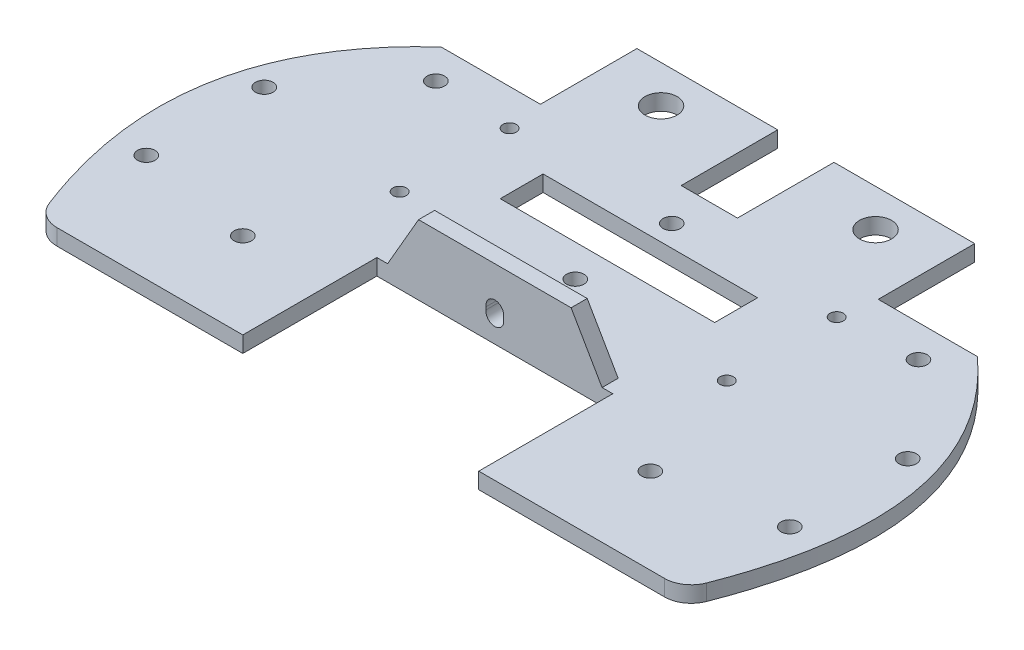
SolidWorks part; units mm, degrees
ref_plane "Front Plane" through (0, 0, 0) normal (0, 0, 1) x (1, 0, 0)
ref_plane "Top Plane" through (0, 0, 0) normal (0, 1, 0) x (1, 0, 0)
ref_plane "Right Plane" through (0, 0, 0) normal (1, 0, 0) x (0, 0, -1)
sketch "Sketch1" plane through (0, 0, 0) normal (0, 1, 0) x (1, 0, 0)
  line L0 (0, 0) -> (24.3409, 0) construction
  line L1 (-31.5, -11) -> (31.5, -11)
  line L2 (-31.5, -11) -> (-31.5, 11)
  line L3 (-31.5, 11) -> (31.5, 11)
  line L4 (31.5, -11) -> (31.5, 11)
  line L5 (-31.5, -11) -> (31.5, 11) construction
  line L6 (-31.5, 11) -> (31.5, -11) construction
  line L7 (0, 0) -> (0, 29.903) construction
  line L8 (-50, -11) -> (50, -11)
  line L9 (-5.25, 11) -> (5.25, 11)
  line L10 (-5.25, 11) -> (-5.25, -11)
  line L11 (-5.25, -11) -> (5.25, -11)
  line L12 (5.25, 11) -> (5.25, -11)
  line L13 (-5.25, 11) -> (5.25, -11) construction
  line L14 (-5.25, -11) -> (5.25, 11) construction
  line L15 (-60, -76) -> (60, -76)
  line L16 (-115.1518, -60) -> (108.3156, -60) construction
  line L28 (-22, -51) -> (22, -51)
  line L29 (-22, -51) -> (-22, -76)
  line L30 (-22, -76) -> (22, -76)
  line L31 (22, -51) -> (22, -76)
  line L32 (-22, -51) -> (22, -76) construction
  line L33 (-22, -76) -> (22, -51) construction
  circle A0 centre (-20, 0) radius 3
  circle A1 centre (20, 0) radius 3
  spline S0 degree 2 poles (-50, -11) (-77.2307, -35.6586) (-60, -76) knots 0 0 0 1 1 1
  spline S1 degree 2 poles (50, -11) (77.2307, -35.6586) (60, -76) knots 0 0 0 1 1 1
  point P0 (0, 0)
  point P13 (0, 0)
  point P20 (0, -11)
  point P23 (0, -76)
  point P40 (0, -63.5)
  dimension "D2" = 6
  dimension "D1" = 63
  dimension "D3" = 20
  dimension "D4" = 10.5
  dimension "D5" = 22
  dimension "D6" = 120
  dimension "D8" = 65
  dimension "D13" = 16
  dimension "D14" = 44
  dimension "D15" = 25
extrude "Boss-Extrude1" add sketch "Sketch1" along normal blind 3
fillet "Fillet1" radius 5 2 edges at (-60, 1.5, 76) (60, 1.5, 76)
sketch "Sketch2" plane through (0, 3, 0) normal (0, 1, 0) x (1, 0, 0)
  line L0 (0, 0) -> (0, -132.9136) construction
  line L1 (-56.6417, -76) -> (-22, -76) construction
  line L2 (0, -17) -> (-58.0491, -17) construction
  line L3 (-63.5757, -34) -> (6.6182, -34) construction
  line L5 (-5.25, -11) -> (5.25, -11) construction
  line L6 (-50, -11) -> (-31.5, -11) construction
  circle A0 centre (-60, -56) radius 1.625
  circle A1 centre (60, -56) radius 1.625
  circle A2 centre (-45, -17) radius 1.625
  circle A3 centre (-60, -34) radius 1.625
  circle A4 centre (60, -34) radius 1.625
  circle A5 centre (45, -17) radius 1.625
  circle A6 centre (0, -18) radius 1.625
  circle A7 centre (0, -36) radius 1.625
  dimension "D3" = 3.25
  dimension "D5" = 18
  dimension "D1" = 60
  dimension "D2" = 20
  dimension "D4" = 6
  dimension "D6" = 45
  dimension "D7" = 60
  dimension "D8" = 23
  dimension "D9" = 7
extrude "Cut-Extrude1" cut sketch "Sketch2" against normal up to surface (3 mm away) up to face at (0, 0, 28.5141)
sketch "Sketch3" plane through (0, 3, 0) normal (0, 1, 0) x (1, 0, 0)
  line L2 (0, 0) -> (0, -162.7456) construction
  line L3 (0, -76) -> (-36.7508, -76) construction
  line L4 (-5.25, -11) -> (5.25, -11) construction
  circle A11 centre (-38, -60) radius 1.625
  circle A12 centre (-60, -56) radius 1.625 construction
  circle A13 centre (38, -60) radius 1.625
  dimension "D1" = 38
  dimension "D2" = 16
  dimension "D6" = 65
sketch "Sketch5" plane through (0, 3, 0) normal (0, 1, 0) x (1, 0, 0)
  line L0 (0, 0) -> (0, -132.0496) construction
  line L1 (-10, -48) -> (10, -48)
  line L2 (-10, -48) -> (-10, -51)
  line L3 (-10, -51) -> (10, -51)
  line L4 (10, -48) -> (10, -51)
  line L5 (-10, -48) -> (10, -51) construction
  line L6 (-10, -51) -> (10, -48) construction
  line L8 (-22, -51) -> (22, -51) construction
  point P0 (0, -49.5)
  dimension "D1" = 3
  dimension "D2" = 20
extrude "Boss-Extrude2" add sketch "Sketch5" along normal blind 10
sketch "Sketch6" plane through (0, 0, 76) normal (0, 0, 1) x (1, 0, 0)
  line L0 (0, 0) -> (0, 11) construction
  line L1 (-56.6417, 0) -> (-22, 0) construction
  circle A0 centre (0, 5) radius 1.65
  circle A1 centre (0, 5.5) radius 1.65
  circle A2 centre (0, 4.5) radius 1.65
  dimension "D2" = 3.3
  dimension "D1" = 5
  dimension "D3" = 0.5
  dimension "D4" = 0.5
extrude "Cut-Extrude4" cut sketch "Sketch6" against normal up to surface (28 mm away) contours L0 A0 A1 | A0 L0 A1 | A2 L0 A0 A1 | L0 A2 A1 A0 | A1 L0 A2 | L0 A1 A2 | A0 L0 A1 A2 | A2 L0 A0 | L0 A2 A0 | L0 A0 A2 A1 | A2 A1 A0 | A2 A0 A1 up to face at (0, 8, 48)
chamfer "Chamfer1" distance 10 angle 60 4 edges at (-10, 3, 49.5) (-10, 13, 49.5) (10, 3, 49.5) (10, 13, 49.5)
sketch "Sketch9" plane through (0, 3, 0) normal (0, 1, 0) x (1, 0, 0)
  line L0 (20, -48) -> (0.6874, -48) construction
  line L1 (-10, -43) -> (10, -43)
  line L2 (-10, -43) -> (-10, -48)
  line L3 (-10, -48) -> (10, -48)
  line L4 (10, -43) -> (10, -48)
  line L5 (-10, -43) -> (10, -48) construction
  line L6 (-10, -48) -> (10, -43) construction
  line L8 (0, 0) -> (0, -249.3966) construction
  point P0 (0, -45.5)
  dimension "D1" = 5
  dimension "D2" = 20
extrude "Cut-Extrude6" cut sketch "Sketch9" against normal up to surface (3 mm away) up to face at (0, 0, 37.625)
fillet "Fillet3" radius 5 2 edges at (-10, 1.5, 43) (10, 1.5, 43)
sketch "Sketch16" plane through (0, 3, 0) normal (0, 1, 0) x (1, 0, 0)
  line L0 (0, 0) -> (0, -90.8851) construction
  line L1 (-20, -22) -> (20, -22)
  line L2 (-20, -22) -> (-20, -30)
  line L3 (-20, -30) -> (20, -30)
  line L4 (20, -22) -> (20, -30)
  line L5 (-20, -22) -> (20, -30) construction
  line L6 (-20, -30) -> (20, -22) construction
  line L7 (-5.25, -11) -> (5.25, -11) construction
  point P0 (0, -26)
  dimension "D1" = 40
  dimension "D2" = 8
  dimension "D3" = 15
extrude "Cut-Extrude11" cut sketch "Sketch16" against normal blind 10
sketch "Sketch17" plane through (0, 3, 0) normal (0, 1, 0) x (1, 0, 0)
  line L0 (0, 0) -> (0, -88.0735) construction
  line L1 (-30.5, -17.75) -> (30.5, -17.75)
  line L2 (-30.5, -17.75) -> (-30.5, -38.25)
  line L3 (-30.5, -38.25) -> (30.5, -38.25)
  line L4 (30.5, -17.75) -> (30.5, -38.25)
  line L5 (-30.5, -17.75) -> (30.5, -38.25) construction
  line L6 (-30.5, -38.25) -> (30.5, -17.75) construction
  line L7 (0, -28) -> (-79.2118, -28) construction
  line L8 (-5.25, -11) -> (5.25, -11) construction
  circle A0 centre (-30.5, -17.75) radius 1.25
  circle A1 centre (-30.5, -38.25) radius 1.25
  circle A2 centre (30.5, -38.25) radius 1.25
  circle A3 centre (30.5, -17.75) radius 1.25
  point P0 (0, -28)
  dimension "D3" = 2.5
  dimension "D1" = 61
  dimension "D2" = 20.5
  dimension "D4" = 17
extrude "Cut-Extrude12" cut sketch "Sketch17" against normal blind 10 contours A0 | A1 | A2 | A3
sketch "Sketch18" plane through (0, 3, 0) normal (0, 1, 0) x (1, 0, 0)
  line L0 (-31.5, 11) -> (-5.25, 11) construction
  line L1 (-61.4162, 11) -> (53.1278, 11)
  line L2 (-61.4162, 11) -> (-61.4162, 7)
  line L3 (-61.4162, 7) -> (53.1278, 7)
  line L4 (53.1278, 11) -> (53.1278, 7)
  line L5 (-61.4162, 11) -> (53.1278, 7) construction
  line L6 (-61.4162, 7) -> (53.1278, 11) construction
  point P0 (-4.1442, 9)
  dimension "D1" = 4
extrude "Cut-Extrude13" cut sketch "Sketch18" against normal blind 10
extrude "Cut-Extrude14" cut sketch "Sketch3" against normal blind 10
equation "\"10.005mmmm\"=10"
